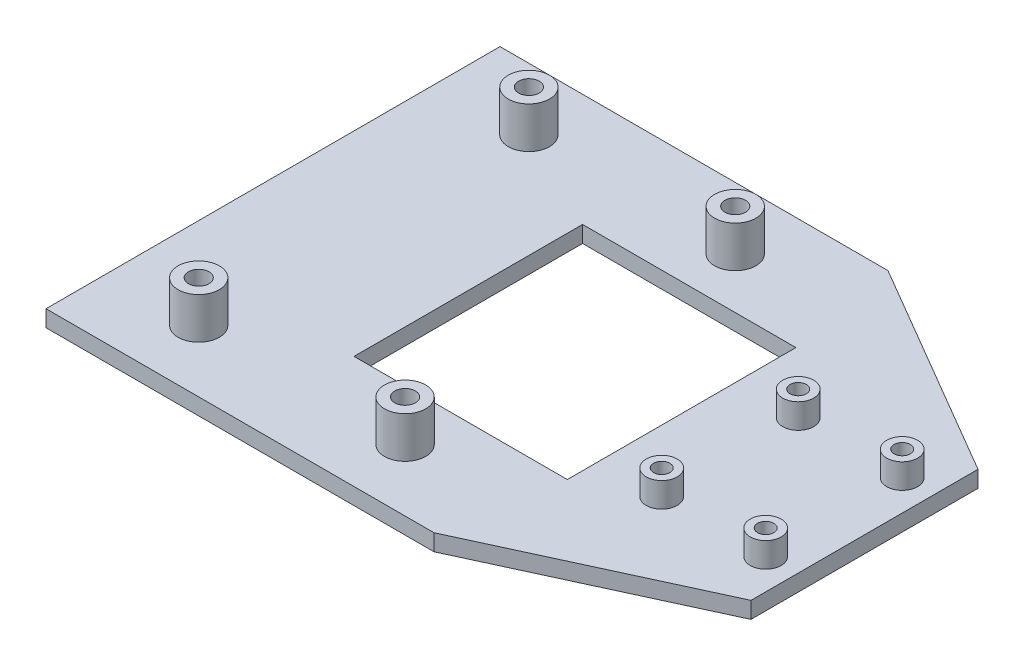
SolidWorks part; units mm, degrees
ref_plane "Front Plane" through (0, 0, 0) normal (0, 0, 1) x (1, 0, 0)
ref_plane "Top Plane" through (0, 0, 0) normal (0, 1, 0) x (1, 0, 0)
ref_plane "Right Plane" through (0, 0, 0) normal (1, 0, 0) x (0, 0, -1)
sketch "Sketch1" plane through (0, 0, 0) normal (0, 1, 0) x (1, 0, 0)
  line L0 (63.245, 15.3764) -> (29.845, 34.925)
  line L1 (-15.875, -25.4) -> (15.875, -25.4) construction
  line L2 (-15.875, -25.4) -> (-15.875, 25.4) construction
  line L3 (-15.875, 25.4) -> (15.875, 25.4) construction
  line L4 (15.875, -25.4) -> (15.875, 25.4) construction
  line L5 (-15.875, -25.4) -> (15.875, 25.4) construction
  line L6 (-15.875, 25.4) -> (15.875, -25.4) construction
  line L7 (29.845, -34.925) -> (-29.845, -34.925)
  line L8 (29.845, -34.925) -> (29.845, 34.925) construction
  line L9 (29.845, 34.925) -> (-29.845, 34.925)
  line L10 (-29.845, -34.925) -> (-29.845, 34.925)
  line L11 (29.845, -34.925) -> (-29.845, 34.925) construction
  line L12 (29.845, 34.925) -> (-29.845, -34.925) construction
  line L13 (42.545, -12.5861) -> (58.545, -12.5861) construction
  line L14 (42.545, -12.5861) -> (42.545, 8.4139) construction
  line L15 (42.545, 8.4139) -> (58.545, 8.4139) construction
  line L16 (58.545, -12.5861) -> (58.545, 8.4139) construction
  line L17 (42.545, -12.5861) -> (58.545, 8.4139) construction
  line L18 (42.545, 8.4139) -> (58.545, -12.5861) construction
  line L19 (37.845, 15.3764) -> (63.245, 15.3764) construction
  line L20 (37.845, 15.3764) -> (37.845, -19.5486) construction
  line L21 (37.845, -19.5486) -> (63.245, -19.5486) construction
  line L22 (63.245, 15.3764) -> (63.245, -19.5486)
  line L23 (37.845, 15.3764) -> (63.245, -19.5486) construction
  line L24 (37.845, -19.5486) -> (63.245, 15.3764) construction
  line L25 (63.245, -19.5486) -> (29.845, -34.925)
  circle A0 centre (-15.875, 25.4) radius 1.5875
  circle A1 centre (15.875, 25.4) radius 1.5875
  circle A2 centre (15.875, -25.4) radius 1.5875
  circle A3 centre (-15.875, -25.4) radius 1.5875
  circle A4 centre (58.545, 8.4139) radius 1.25
  circle A5 centre (58.545, -12.5861) radius 1.25
  circle A6 centre (42.545, -12.5861) radius 1.25
  circle A8 centre (42.545, 8.4139) radius 1.25
  point P0 (0, 0)
  point P7 (0, 0)
  point P15 (50.545, -2.0861)
  point P23 (50.545, -2.0861)
  dimension "D3" = 3.175
  dimension "D8" = 2.5
  dimension "D1" = 50.8
  dimension "D2" = 31.75
  dimension "D4" = 69.85
  dimension "D5" = 13.97
  dimension "D6" = 21
  dimension "D7" = 16
  dimension "D9" = 25.4
  dimension "D10" = 34.925
  dimension "D11" = 12.7
extrude "Boss-Extrude1" add sketch "Sketch1" along normal blind 2.54
sketch "Sketch2" plane through (0, 2.54, 0) normal (0, 1, 0) x (1, 0, 0)
  line L5 (29.845, 17.582) -> (33.02, 17.582)
  line L6 (29.845, 17.582) -> (0.2018, 17.582)
  line L7 (29.845, 17.582) -> (29.845, -17.582) construction
  line L8 (29.845, 17.582) -> (29.845, -17.582) construction
  line L9 (29.845, -17.582) -> (0.2018, -17.582)
  line L10 (0.2018, 17.582) -> (0.2018, -17.582)
  line L11 (29.845, 17.582) -> (0.2018, -17.582) construction
  line L12 (29.845, -17.582) -> (0.2018, 17.582) construction
  line L13 (29.845, -17.582) -> (33.02, -17.582)
  line L14 (33.02, 17.582) -> (33.02, -17.582)
  point P0 (0, 0)
  point P1 (15.0234, 0)
  dimension "D1" = 3.175
extrude "Cut-Extrude1" cut sketch "Sketch2" against normal blind 2.54
sketch "Sketch3" plane through (0, 2.54, 0) normal (0, 1, 0) x (1, 0, 0)
  circle A0 centre (58.545, 8.4139) radius 1.25 construction
  circle A1 centre (42.545, 8.4139) radius 1.25 construction
  circle A2 centre (58.545, 8.4139) radius 2.3813
  circle A3 centre (42.545, -12.5861) radius 1.25 construction
  circle A4 centre (58.545, -12.5861) radius 2.3813
  circle A5 centre (42.545, -12.5861) radius 2.3812
  circle A6 centre (58.545, -12.5861) radius 1.25 construction
  circle A10 centre (58.545, -12.5861) radius 1.25
  circle A11 centre (42.545, -12.5861) radius 1.25
  circle A12 centre (42.545, 8.4139) radius 1.25
  circle A13 centre (58.545, 8.4139) radius 1.25
  circle A14 centre (42.545, 8.4139) radius 2.3812
  point P15 (16.2731, 25.4)
  point P36 (15.312, -25.4)
  point P38 (-16.4319, -25.4)
  dimension "D1" = 4.7625
  dimension "D2" = 4.7625
  dimension "D3" = 4.7625
  dimension "D4" = 4.7625
extrude "Boss-Extrude2" add sketch "Sketch3" along normal blind 3.81
sketch "Sketch5" plane through (0, 2.54, 0) normal (0, 1, 0) x (1, 0, 0)
  circle A0 centre (15.875, -25.4) radius 1.5875
  circle A1 centre (-15.875, -25.4) radius 1.5875
  circle A2 centre (-15.875, 25.4) radius 1.5875
  circle A3 centre (15.875, 25.4) radius 1.5875
  circle A4 centre (-15.875, 25.4) radius 3.175
  circle A5 centre (15.875, 25.4) radius 3.175
  circle A6 centre (15.875, -25.4) radius 3.175
  circle A7 centre (-15.875, -25.4) radius 3.175
  point P12 (-15.875, -25.4)
  point P14 (15.875, -25.4)
  point P16 (15.875, 25.4)
  point P18 (-15.875, 25.4)
  dimension "D1" = 6.35
extrude "Boss-Extrude3" add sketch "Sketch5" along normal blind 6.35
